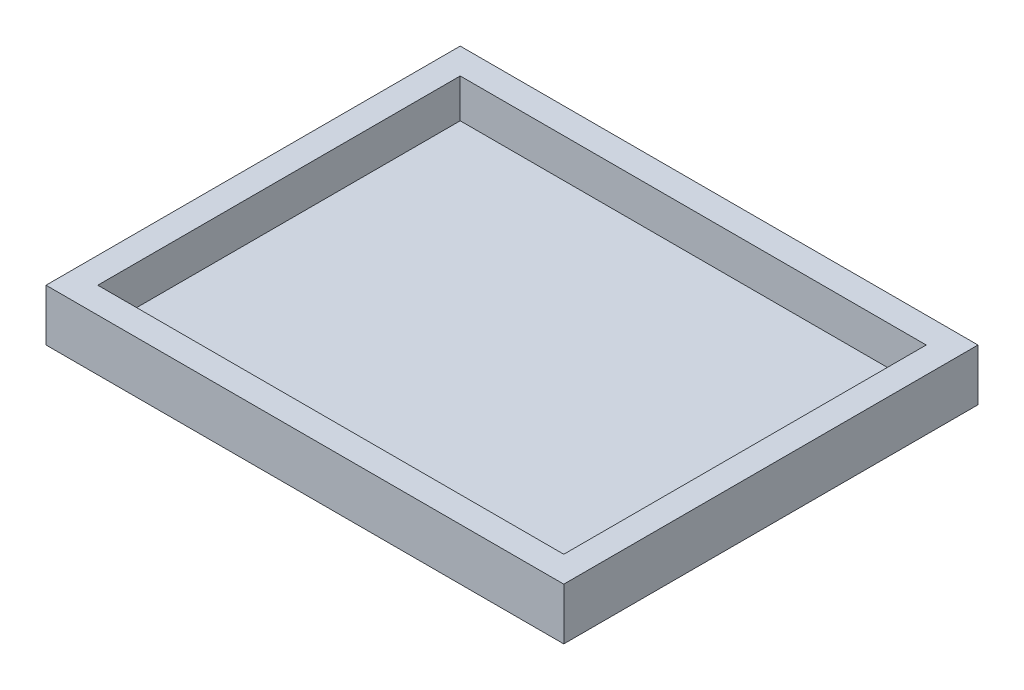
SolidWorks part; units mm, degrees
ref_plane "Front Plane" through (0, 0, 0) normal (0, 0, 1) x (1, 0, 0)
ref_plane "Top Plane" through (0, 0, 0) normal (0, 1, 0) x (1, 0, 0)
ref_plane "Right Plane" through (0, 0, 0) normal (1, 0, 0) x (0, 0, -1)
sketch "Sketch1" plane through (0, 0, 0) normal (0, 1, 0) x (1, 0, 0)
  line L0 (-45, 35) -> (-45, -35)
  line L1 (-50, 40) -> (50, 40)
  line L2 (-50, 40) -> (-50, -40)
  line L3 (-50, -40) -> (50, -40)
  line L4 (50, 40) -> (50, -40)
  line L5 (-50, 40) -> (50, -40) construction
  line L6 (-50, -40) -> (50, 40) construction
  line L7 (-45, -35) -> (45, -35)
  line L8 (45, 35) -> (45, -35)
  line L9 (-45, 35) -> (45, 35)
  point P0 (0, 0)
  dimension "D1" = 80
  dimension "D2" = 100
  dimension "D3" = 5
extrude "Boss-Extrude1" add sketch "Sketch1" along normal blind 10
extrude "Boss-Extrude2" add sketch "Sketch1<2>" along normal blind 2.5 contours L9 L0 L7 L8 region at (0, 0, 0)
sketch "Sketch1<2>" plane through (0, 0, 0) normal (0, 1, 0) x (1, 0, 0) same geometry as "Sketch1"
